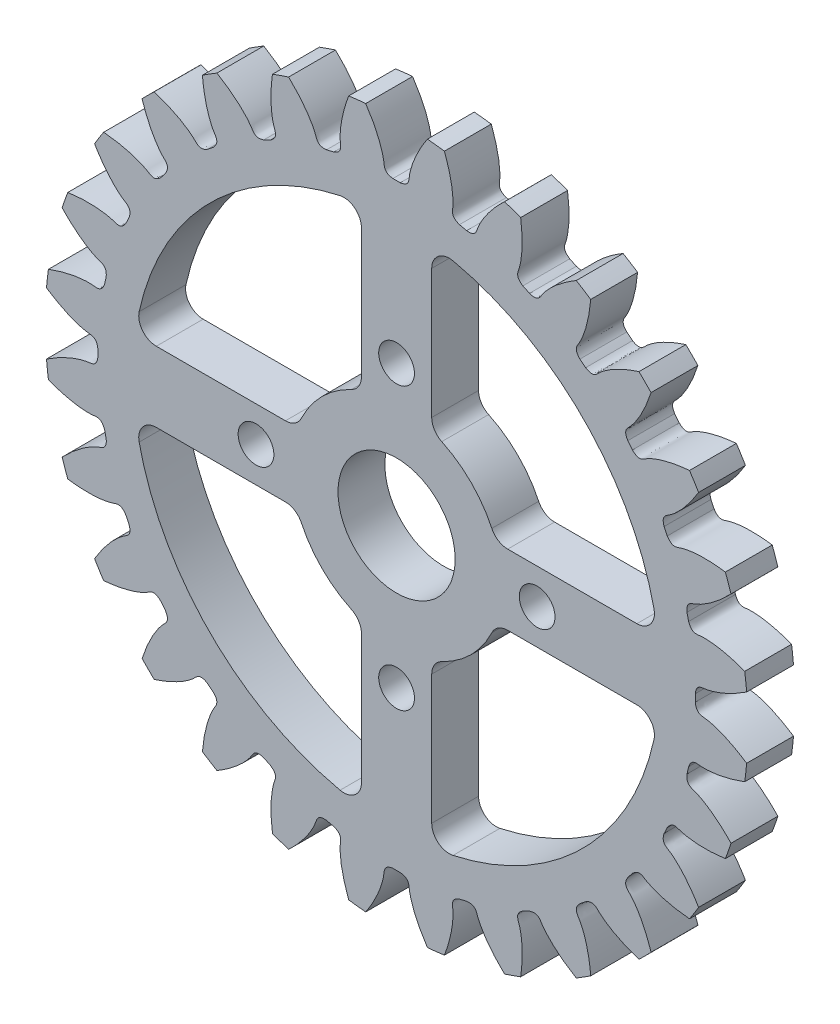
SolidWorks part; units mm, degrees
material "Thornel Mat VMA"
ref_plane "前视基准面" through (0, 0, 0) normal (0, 0, 1) x (1, 0, 0)
ref_plane "上视基准面" through (0, 0, 0) normal (0, 1, 0) x (1, 0, 0)
ref_plane "右视基准面" through (0, 0, 0) normal (1, 0, 0) x (0, 0, -1)
other "Configuration Table"
sketch "草图1" plane through (0, 0, 0) normal (0, 0, 1) x (1, 0, 0)
  circle A0 centre (0, 0) radius 30
extrude "凸台-拉伸1" add sketch "草图1" along normal blind 4
ref_axis "基准轴1" through (0, 0, -1.5) along (0, 0, 1)
sketch "草图2" plane through (0, 0, 0) normal (0, 0, 1) x (1, 0, 0)
  line L0 (0, 0) -> (0, 30) construction
  circle A0 centre (0, 0) radius 30 construction
  arc A1 (0.3132, 25.4981) -> (-0.3132, 25.4981) centre (0, 0) ccw
  arc A2 (6.5865, 34.0723) -> (-6.5865, 34.0723) centre (0, 0) ccw
  spline S0 degree 3 poles (0.3132, 25.4981) (1.0885, 25.5993) (1.0394, 26.0374) (1.1076, 26.4805) (1.1193, 26.5479) (1.1344, 26.6254) (1.1532, 26.7129) (1.1762, 26.8102) (1.2037, 26.9172) (1.2362, 27.0338) (1.274, 27.1598) (1.3176, 27.2951) (1.3672, 27.4394) (1.4234, 27.5925) (1.4865, 27.7543) (1.5567, 27.9246) (1.6346, 28.1031) (1.7205, 28.2895) (1.8146, 28.4836) (1.9174, 28.6852) (2.0291, 28.894) (2.1502, 29.1097) (2.2809, 29.332) (2.4215, 29.5606) (2.5723, 29.7952) (2.7337, 30.0355) (2.9059, 30.2811) (3.0891, 30.5318) (3.2838, 30.787) (3.49, 31.0466) (3.7081, 31.3101) (3.9383, 31.5772) (4.1808, 31.8475) (4.4359, 32.1205) (4.7037, 32.3959) (4.9844, 32.6734) (5.2783, 32.9524) (5.5855, 33.2325) (6.0183, 33.6117) (6.3554, 33.8894) (6.5865, 34.0723) knots 0 0 0 0 0.112672 0.118023 0.124348 0.131645 0.139915 0.149158 0.159374 0.170563 0.182724 0.195859 0.209967 0.225048 0.241101 0.258128 0.276127 0.2951 0.315045 0.335964 0.357855 0.380719 0.404556 0.429367 0.45515 0.481906 0.509635 0.538337 0.568012 0.598659 0.63028 0.662874 0.696441 0.73098 0.766493 0.802978 0.840437 0.878868 0.918272 1 1 1 1
  spline S1 degree 3 poles (-0.3132, 25.4981) (-1.0885, 25.5993) (-1.0394, 26.0374) (-1.1076, 26.4805) (-1.1193, 26.5479) (-1.1344, 26.6254) (-1.1532, 26.7129) (-1.1762, 26.8102) (-1.2037, 26.9172) (-1.2362, 27.0338) (-1.274, 27.1598) (-1.3176, 27.2951) (-1.3672, 27.4394) (-1.4234, 27.5925) (-1.4865, 27.7543) (-1.5567, 27.9246) (-1.6346, 28.1031) (-1.7205, 28.2895) (-1.8146, 28.4836) (-1.9174, 28.6852) (-2.0291, 28.894) (-2.1502, 29.1097) (-2.2809, 29.332) (-2.4215, 29.5606) (-2.5723, 29.7952) (-2.7337, 30.0355) (-2.9059, 30.2811) (-3.0891, 30.5318) (-3.2838, 30.787) (-3.49, 31.0466) (-3.7081, 31.3101) (-3.9383, 31.5772) (-4.1808, 31.8475) (-4.4359, 32.1205) (-4.7037, 32.3959) (-4.9844, 32.6734) (-5.2783, 32.9524) (-5.5855, 33.2325) (-6.0183, 33.6117) (-6.3554, 33.8894) (-6.5865, 34.0723) knots 0 0 0 0 0.112672 0.118023 0.124348 0.131645 0.139915 0.149158 0.159374 0.170563 0.182724 0.195859 0.209967 0.225048 0.241101 0.258128 0.276127 0.2951 0.315045 0.335964 0.357855 0.380719 0.404556 0.429367 0.45515 0.481906 0.509635 0.538337 0.568012 0.598659 0.63028 0.662874 0.696441 0.73098 0.766493 0.802978 0.840437 0.878868 0.918272 1 1 1 1
extrude "切除-拉伸1" cut sketch "草图2" along normal through all
pattern_circular "阵列(圆周)1" count 28 every 12.857 about axis through (0, 0, -1.5) along (0, 0, 1) of "切除-拉伸1"
sketch "草图3" plane through (0, 0, 0) normal (0, 0, 1) x (1, 0, 0)
  circle A0 centre (0, 0) radius 28 construction
  dimension "Dn" = 56
sketch "草图4" plane through (0, 0, 4) normal (0, 0, 1) x (1, 0, 0)
  circle A0 centre (0, 0) radius 5
  dimension "D1" = 10
extrude "切除-拉伸2" cut sketch "草图4" against normal mid plane 10
sketch "草图5" plane through (0, 0, 4) normal (0, 0, 1) x (1, 0, 0)
  circle A0 centre (0, 0) radius 12 construction
  circle A1 centre (0, 12) radius 1.525
  circle A2 centre (12, 0) radius 1.525
  circle A3 centre (0, -12) radius 1.525
  circle A4 centre (-12, 0) radius 1.525
  point P5 (0.1442, -17.0943)
  point P6 (0, 0)
  point P14 (0, 0)
  dimension "D1" = 24
  dimension "D2" = 3.05
  dimension "D3" = 4
extrude "切除-拉伸3" cut sketch "草图5" against normal up to surface (4 mm away) up to face at (5, 0, 0)
sketch "草图6" plane through (0, 0, 0) normal (0, 0, -1) x (-1, 0, 0)
  line L0 (-22.5, 0) -> (22.5, 0) construction
  line L1 (0, 22.5) -> (0, -22.5) construction
  line L2 (-22.5, -3) -> (22.5, -3)
  line L3 (-3, 22.5) -> (-3, -22.5)
  line L4 (-22.5, 3) -> (22.5, 3)
  line L5 (3, 22.5) -> (3, -22.5)
  circle A0 centre (0, 0) radius 22.5
  circle A1 centre (0, 0) radius 9
  circle A2 centre (0, 0) radius 5 construction
  dimension "D1" = 45
  dimension "D2" = 4
  dimension "D3" = 3
  dimension "D4" = 3
extrude "切除-拉伸4" cut sketch "草图6" against normal up to surface (4 mm away) contours A1 L4 A0 L5 | A1 L5 A0 L2 | A1 L2 A0 L3 | A1 L3 A0 L4 region at (11.3108, -11.3108, 0) region at (11.3108, 11.3108, 0) region at (-11.3108, -11.3108, 0) region at (-11.3108, 11.3108, 0) up to face at (1.525, 12, 4)
fillet "圆角1" radius 1.5 16 edges at (3, 22.2991, 2) (3, 8.4853, 2) (3, -22.2991, 2) (22.2991, -3, 2) (8.4853, -3, 2) (3, -8.4853, 2) (-8.4853, 3, 2) (-3, 8.4853, 2) (-3, 22.2991, 2) (-22.2991, 3, 2) (-3, -8.4853, 2) (-8.4853, -3, 2) (-22.2991, -3, 2) (-3, -22.2991, 2) (22.2991, 3, 2) (8.4853, 3, 2)
